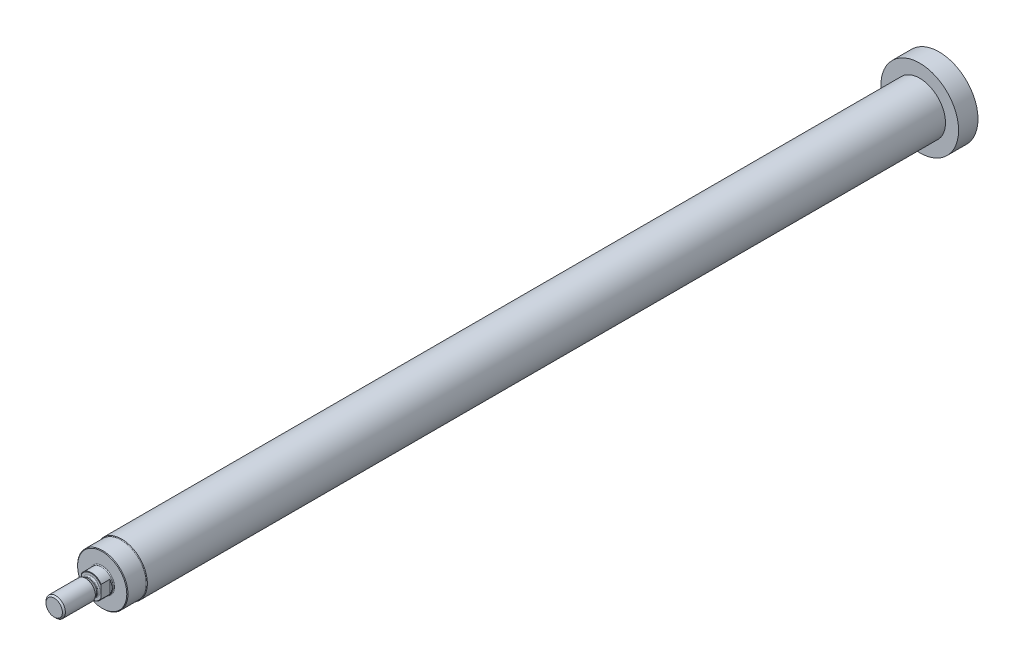
SolidWorks part; units mm, degrees
ref_plane "Front Plane" through (0, 0, 0) normal (0, 0, 1) x (1, 0, 0)
ref_plane "Top Plane" through (0, 0, 0) normal (0, 1, 0) x (1, 0, 0)
ref_plane "Right Plane" through (0, 0, 0) normal (1, 0, 0) x (0, 0, -1)
sketch "Sketch1" plane through (0, 0, 0) normal (1, 0, 0) x (0, 0, -1)
  line L0 (-21.5, 0) -> (-21.5, 5.8)
  line L1 (-21.5, 5.8) -> (-21.3, 6)
  line L2 (-21.3, 6) -> (-16.2, 6)
  line L3 (-15.8, 6.4) -> (-15.8, 12.66)
  line L4 (-15.8, 12.66) -> (-15.5, 12.96)
  line L5 (-15.5, 12.96) -> (-6.1, 12.96)
  line L6 (-5.8, 13.26) -> (405, 13.26)
  line L7 (405, 13.26) -> (405, 20)
  line L8 (405, 20) -> (415, 20)
  line L9 (415, 20) -> (415, 0)
  line L10 (415, 0) -> (-21.5, 0)
  line L11 (415, 0) -> (-21.5, 0) construction
  arc A0 (-16.2, 6) -> (-15.8, 6.4) centre (-16.2, 6.4) ccw
  arc A1 (-6.1, 12.96) -> (-5.8, 13.26) centre (-6.1, 13.26) ccw
revolve "Revolve1" add sketch "Sketch1" angle 360 about L11 reverse direction yes
sketch "Sketch2" plane through (0, 0, 0) normal (1, 0, 0) x (0, 0, -1)
  line L0 (-40.5, 0) -> (-40.5, 4.233)
  line L1 (-40.5, 4.233) -> (-39.733, 5)
  line L2 (-39.733, 5) -> (-24.3321, 5)
  line L3 (-24.3321, 5) -> (-22.7392, 4.0804)
  line L4 (-22.4392, 4) -> (-22.1, 4)
  line L5 (-21.5, 4.6) -> (-21.5, 0)
  line L6 (-21.5, 0) -> (-40.5, 0)
  line L7 (-21.5, 0) -> (-40.5, 0) construction
  arc A0 (-22.7392, 4.0804) -> (-22.4392, 4) centre (-22.4392, 4.6) ccw
  arc A1 (-22.1, 4) -> (-21.5, 4.6) centre (-22.1, 4.6) ccw
revolve "Revolve2" add sketch "Sketch2" angle 360 about L7 reverse direction yes
cosmetic thread "Cosmetic Thread1" parameters "D1"=17.7608, "D2"=8.466
ref_plane "Plane1" through (0, 0, 21.5) normal (0, 0, 1) x (1, 0, 0)
sketch "Sketch3" plane through (0, 0, 21.5) normal (0, 0, 1) x (1, 0, 0)
  line L0 (-7, 8) -> (-7, -6)
  line L1 (-7, -6) -> (-5, -6)
  line L2 (-5, -6) -> (-5, 6)
  line L3 (-5, 6) -> (5, 6)
  line L4 (5, 6) -> (5, -6)
  line L5 (5, -6) -> (7, -6)
  line L6 (7, -6) -> (7, 8)
  line L7 (7, 8) -> (-7, 8)
extrude "Cut-Extrude1" cut sketch "Sketch3" against normal blind 4.7
ref_plane "Plane2" through (0, 0, 31) normal (0, 0, 1) x (1, 0, 0)
ref_plane "Plane3" through (0, 0, 21.5) normal (0, 0, 1) x (1, 0, 0)
ref_plane "EAGF XY" through (0, 0, 21.5) normal (0, 0, -1) x (-1, 0, 0)
ref_plane "EAGF XZ" through (0, 0, 0) normal (0, 1, 0) x (1, 0, 0)
ref_plane "EAGF YZ" through (0, 0, 0) normal (1, 0, 0) x (0, 0, -1)
ref_axis "EAGF X" through (-80.9, 0, 21.5) along (1, 0, 0)
ref_axis "EAGF Y" through (0, 50, 21.5) along (0, -1, 0)
ref_axis "EAGF Z" through (0, 0, -80.9) along (0, 0, 1)
sketch3d "EAGF"
  point P0 (0, 0, 21.5)
ref_plane "EPCO_KS XY" through (0, 0, 0) normal (0, 0, -1) x (-1, 0, 0)
ref_plane "EPCO_KS XZ" through (0, 0, 0) normal (0, 1, 0) x (1, 0, 0)
ref_plane "EPCO_KS YZ" through (0, 0, 0) normal (1, 0, 0) x (0, 0, -1)
ref_axis "EPCO_KS X" through (-80.9, 0, 0) along (1, 0, 0)
ref_axis "EPCO_KS Y" through (0, 50, 0) along (0, -1, 0)
ref_axis "EPCO_KS Z" through (0, 0, -80.9) along (0, 0, 1)
sketch3d "EPCO_KS"
  point P0 (0, 0, 0)
ref_plane "NUT XY" through (0, 0, 31) normal (0, 0, -1) x (-1, 0, 0)
ref_plane "NUT XZ" through (0, 0, 0) normal (0, 1, 0) x (1, 0, 0)
ref_plane "NUT YZ" through (0, 0, 0) normal (1, 0, 0) x (0, 0, -1)
ref_axis "NUT X" through (-80.9, 0, 31) along (1, 0, 0)
ref_axis "NUT Y" through (0, 50, 31) along (0, -1, 0)
ref_axis "NUT Z" through (0, 0, -80.9) along (0, 0, 1)
sketch3d "NUT"
  point P0 (0, 0, 31)
other "Freeze***"
